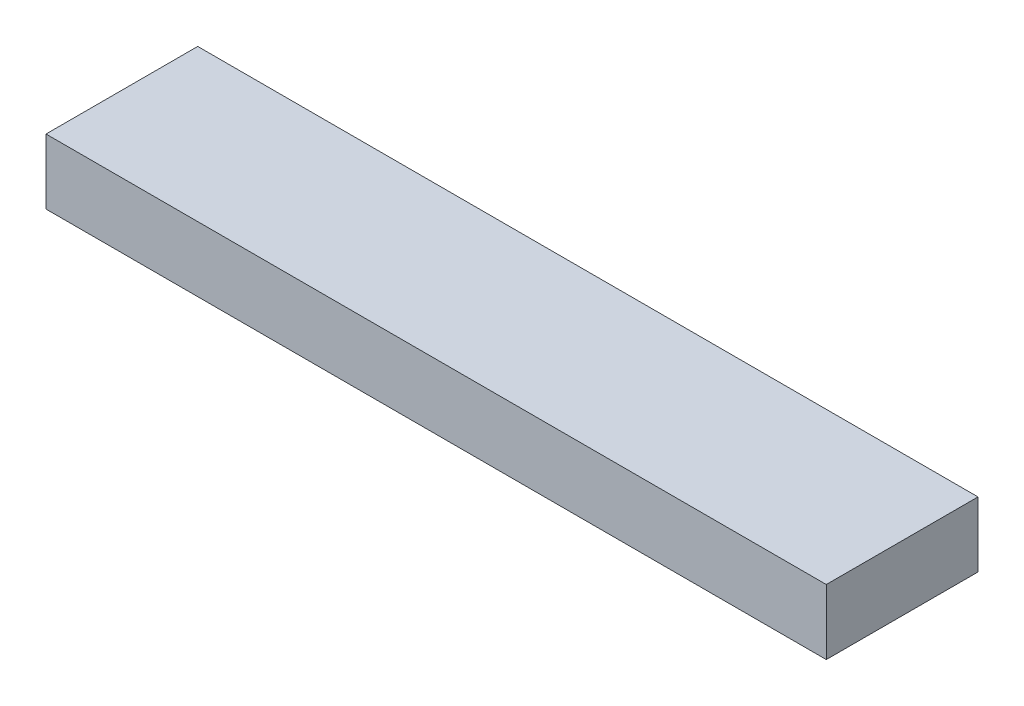
SolidWorks part; units mm, degrees
ref_plane "Front Plane" through (0, 0, 0) normal (0, 0, 1) x (1, 0, 0)
ref_plane "Top Plane" through (0, 0, 0) normal (0, 1, 0) x (1, 0, 0)
ref_plane "Right Plane" through (0, 0, 0) normal (1, 0, 0) x (0, 0, -1)
sketch "Sketch1" plane through (0, 0, 0) normal (0, 1, 0) x (1, 0, 0)
  line L1 (-56.46, 10.4673) -> (400.74, 10.4673)
  line L2 (-56.46, 10.4673) -> (-56.46, -78.4327)
  line L3 (-56.46, -78.4327) -> (400.74, -78.4327)
  line L4 (400.74, 10.4673) -> (400.74, -78.4327)
  dimension "D1" = 88.9
  dimension "D2" = 457.2
extrude "Boss-Extrude1" add sketch "Sketch1" along normal blind 38.1
